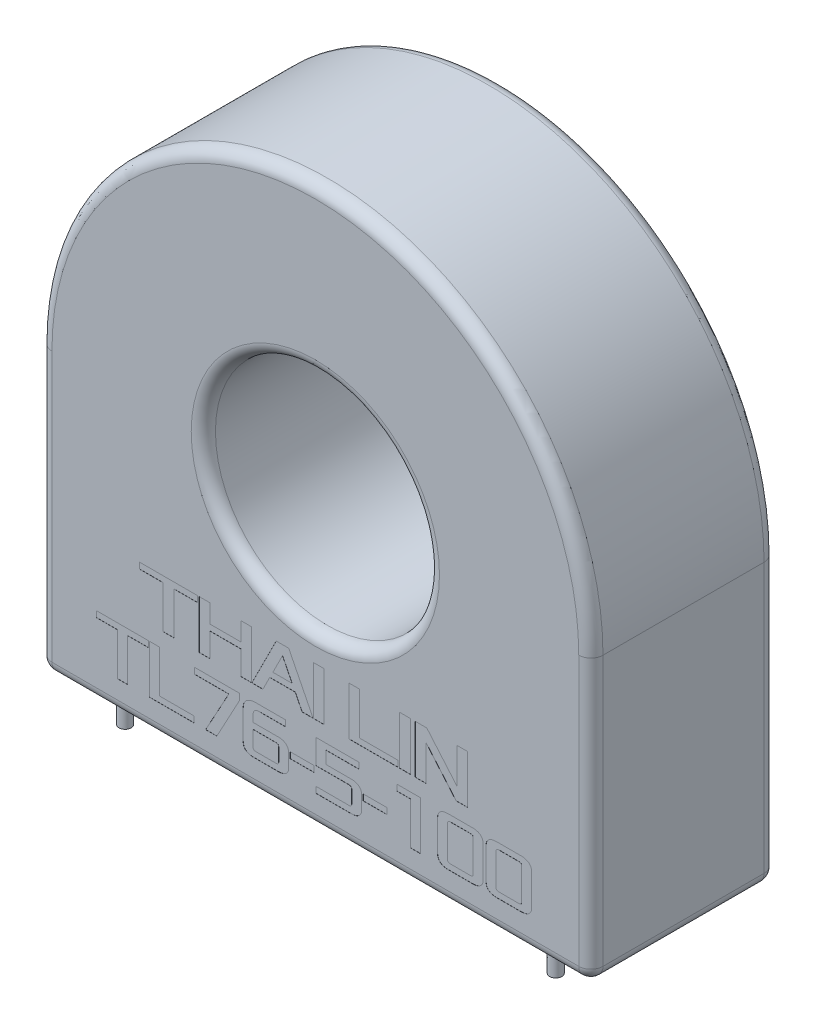
SolidWorks part; units mm, degrees
ref_plane "Front Plane" through (0, 0, 0) normal (0, 0, 1) x (1, 0, 0)
ref_plane "Top Plane" through (0, 0, 0) normal (0, 1, 0) x (1, 0, 0)
ref_plane "Right Plane" through (0, 0, 0) normal (1, 0, 0) x (0, 0, -1)
sketch "Sketch1" plane through (0, 0, 0) normal (0, 0, 1) x (1, 0, 0)
  line L0 (0, 56.047) -> (0, -94.9477) construction
  line L1 (0, 34.375) -> (50.579, 34.375) construction
  line L2 (-22.75, 11.625) -> (22.75, 11.625) construction
  line L3 (-22.75, 11.625) -> (-22.75, -11.625)
  line L4 (-22.75, -11.625) -> (22.75, -11.625)
  line L5 (22.75, 11.625) -> (22.75, -11.625)
  line L6 (-22.75, 11.625) -> (22.75, -11.625) construction
  line L7 (-22.75, -11.625) -> (22.75, 11.625) construction
  arc A0 (-22.75, 11.625) -> (22.75, 11.625) centre (0, 11.625) cw
  circle A1 centre (0, 11.625) radius 9.25
  point P2 (0, 0)
  dimension "D1" = 45.5
  dimension "D3" = 18.5
  dimension "D2" = 46
extrude "Boss-Extrude1" add sketch "Sketch1" along normal mid plane 15.3
sketch "Sketch2" plane through (0, -11.625, 0) normal (0, -1, 0) x (1, 0, 0)
  line L0 (0, 13.15) -> (0, 0) construction
  line L1 (0, 0) -> (25.5661, 0) construction
  line L2 (17.78, 5.58) -> (28.4302, 5.58) construction
  line L3 (-22.75, 7.65) -> (22.75, 7.65) construction
  circle A0 centre (17.78, 5.58) radius 0.5
  circle A1 centre (0, -4.58) radius 0.5
  circle A2 centre (-17.78, 5.58) radius 0.5
  point P13 (17.78, 5.58)
  point P14 (0, 0)
  dimension "D1" = 10.16
  dimension "D4" = 1
  dimension "D2" = 17.78
  dimension "D3" = 2.07
extrude "Boss-Extrude2" add sketch "Sketch2" along normal mid plane 5
fillet "Fillet1" radius 1 11 edges at (-22.75, 0, -7.65) (0, 34.375, -7.65) (22.75, 0, 7.65) (-22.75, 0, 7.65) (-22.75, -11.625, 0) (22.75, -11.625, 0) (0, -11.625, -7.65) (0, -11.625, 7.65) (22.75, 0, -7.65) (0, 34.375, 7.65) (9.25, 11.625, 7.65)
sketch "Sketch3" plane through (0, 0, 7.65) normal (0, 0, 1) x (1, 0, 0)
  line L0 (-19.836, -3.856) -> (19.836, -3.856) construction
  line L1 (-19.836, -9.106) -> (19.836, -9.106) construction
  text T0 "THAI LIN " font "Xolonium" height 4
  text T1 "TL76-5-100" font "Xolonium" height 4
  point P2 (0, -3.856)
  dimension "D1" = 5.25
extrude "Cut-Extrude1" cut sketch "Sketch3" against normal blind 0.01
sketch "Sketch4" plane through (0, -11.625, 0) normal (0, -1, 0) x (1, 0, 0)
  line L0 (-20.683, 1.3567) -> (20.0523, 1.3567) construction
  line L1 (-4.2604, -3.6891) -> (4.6412, -3.6891) construction
  text T0 "#2                                #1" font "Xolonium" height 3
  text T1 "#3" font "Xolonium" height 3
  point P5 (-20.0642, 1.9279)
  point P6 (-20.3498, 2.2135)
  point P7 (-20.3974, 0.4998)
  point P8 (-20.683, 1.3567)
  point P9 (-4.2604, -3.6891)
  point P10 (0.1904, -3.6891)
extrude "Cut-Extrude2" cut sketch "Sketch4" against normal blind 0.01
